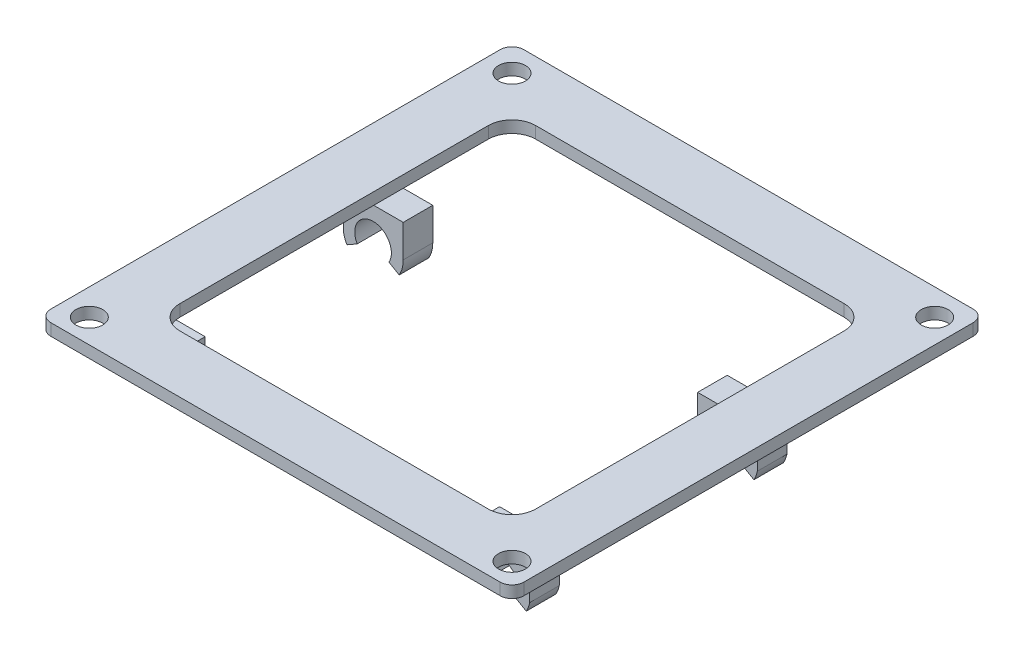
SolidWorks part; units mm, degrees
ref_plane "Front Plane" through (0, 0, 0) normal (0, 0, 1) x (1, 0, 0)
ref_plane "Top Plane" through (0, 0, 0) normal (0, 1, 0) x (1, 0, 0)
ref_plane "Right Plane" through (0, 0, 0) normal (1, 0, 0) x (0, 0, -1)
ref_plane "Plane5" through (0, 1.4, 0) normal (0, 1, 0) x (1, 0, 0)
sketch "Sketch1" plane through (0, 1.4, 0) normal (0, 1, 0) x (1, 0, 0)
  line L0 (-30, 40.97) -> (30, 40.97) construction
  line L1 (35, -16.53) -> (-35, -16.53)
  line L2 (35, -16.53) -> (35, 40.97)
  line L3 (35, 40.97) -> (-35, 40.97)
  line L4 (-35, -16.53) -> (-35, 40.97)
  line L5 (35, -16.53) -> (-35, 40.97) construction
  line L6 (35, 40.97) -> (-35, -16.53) construction
  line L8 (45.85, -16.53) -> (-45.85, -16.53) construction
  line L9 (0, 0) -> (0, 83.8599) construction
  point P0 (-14.8765, 0)
  point P13 (0, 12.22)
  dimension "D1" = 70
extrude "Boss-Extrude1" add sketch "Sketch1" along normal blind 8
sketch "Sketch3" plane through (0, 0, -36.97) normal (0, 0, -1) x (-1, 0, 0)
  line L0 (-35, 1.4) -> (-35, -5.105)
  line L1 (-24.9, -4.1) -> (-24.9, 1.4)
  line L2 (0, 0) -> (0, -23.3047) construction
  line L3 (-35, 1.4) -> (-24.9, 1.4)
  line L4 (-35, 1.4) -> (35, 1.4) construction
  line L5 (35, 1.4) -> (24.9, 1.4)
  line L6 (24.9, -4.1) -> (24.9, 1.4)
  line L7 (35, 1.4) -> (35, -5.105)
  arc A0 (-35, -5.105) -> (-24.9, -4.1) centre (-30, -4.1) ccw
  circle A2 centre (-30, -4.1) radius 3.1
  circle A4 centre (30, -4.1) radius 3.1
  arc A6 (35, -5.105) -> (24.9, -4.1) centre (30, -4.1) cw
  dimension "D1" = 2
  dimension "D2" = 6.2
extrude "Boss-Extrude2" add sketch "Sketch3" against normal blind 5 from offset 2 contours A0 L0 L3 L1 A2 | L7 A6 L6 L5 A4 region at (29.95, 1.2536, -36.97) region at (-34.8536, -1.8525, -36.97) offset against normal yes
ref_plane "Plane1" through (0, 0, -13.22) normal (0, 0, 1) x (1, 0, 0)
mirror "Mirror1" about plane through (0, 0, -13.22) normal (0, 0, 1) of "Boss-Extrude2"
sketch "Sketch4" plane through (0, 0, -29.97) normal (0, 0, -1) x (-1, 0, 0)
  line L0 (-30, -4.1) -> (-20, -9.8735)
  line L1 (-20, -9.8735) -> (-40, -9.8735)
  line L2 (-40, -9.8735) -> (-30, -4.1)
  line L3 (0, 0) -> (0, -31.947) construction
  line L4 (20, -9.8735) -> (40, -9.8735)
  line L5 (30, -4.1) -> (20, -9.8735)
  line L6 (40, -9.8735) -> (30, -4.1)
  dimension "D1" = 20
  dimension "D2" = 120
extrude "Cut-Extrude1" cut sketch "Sketch4" against normal blind 63 and the other way blind 10
other "Move Face1" flip direction yes face at (0, 9.4, -12.22) offset 6 parameters "D1"=6
sketch "Sketch5" plane through (0, 3.4, 0) normal (0, 1, 0) x (1, 0, 0)
  line L0 (-40, -16.53) -> (-35, -16.53) construction
  line L1 (40, 63.47) -> (-40, 63.47)
  line L2 (40, 63.47) -> (40, -16.53)
  line L3 (40, -16.53) -> (-40, -16.53)
  line L4 (-40, 63.47) -> (-40, -16.53)
  line L5 (40, 63.47) -> (-40, -16.53) construction
  line L6 (40, -16.53) -> (-40, 63.47) construction
  line L7 (-35, 40.97) -> (-35, -16.53) construction
  line L8 (35, -16.53) -> (40, -16.53) construction
  line L9 (35, -16.53) -> (35, 40.97) construction
  line L10 (-35, -16.53) -> (35, -16.53) construction
  point P0 (0, 23.47)
  dimension "D1" = 80
  dimension "D2" = 80
extrude "Boss-Extrude3" add sketch "Sketch5" against normal blind 2
fillet "Fillet1" radius 2 4 edges at (-40, 2.4, -63.47) (-40, 2.4, 16.53) (40, 2.4, 16.53) (40, 2.4, -63.47)
sketch "Sketch6" plane through (0, 3.4, 0) normal (0, 1, 0) x (1, 0, 0)
  line L0 (35.9551, 59.0149) -> (39.4142, 62.8842) construction
  line L1 (35.9551, 59.0149) -> (-35.5449, 59.0149) construction
  line L2 (35.9551, 59.0149) -> (35.9551, -12.4851) construction
  line L3 (35.9551, -12.4851) -> (-35.5449, -12.4851) construction
  line L4 (-35.5449, 59.0149) -> (-35.5449, -12.4851) construction
  line L5 (-35.5449, -12.4851) -> (-39.4142, -15.9442) construction
  circle A0 centre (35.9551, 59.0149) radius 2.275
  circle A1 centre (35.9551, -12.4851) radius 2.275
  circle A2 centre (-35.5449, 59.0149) radius 2.275
  circle A3 centre (-35.5449, -12.4851) radius 2.275
  arc A4 (40, 61.47) -> (38, 63.47) centre (38, 61.47) ccw construction
  arc A5 (-40, -14.53) -> (-38, -16.53) centre (-38, -14.53) ccw construction
  dimension "D2" = 4.55
  dimension "D1" = 71.5
extrude "Cut-Extrude2" cut sketch "Sketch6" against normal blind 2
sketch "Sketch7" plane through (0, 3.4, 0) normal (0, 1, 0) x (1, 0, 0)
  line L0 (35.9551, 59.0149) -> (-35.5449, -12.4851) construction
  line L2 (-29.8881, -6.8282) -> (30.2982, -6.8282)
  line L3 (-29.8881, -6.8282) -> (-29.8881, 53.3581)
  line L4 (-29.8881, 53.3581) -> (30.2982, 53.3581)
  line L5 (30.2982, -6.8282) -> (30.2982, 53.3581)
  line L6 (-29.8881, -6.8282) -> (30.2982, 53.3581) construction
  line L7 (-29.8881, 53.3581) -> (30.2982, -6.8282) construction
  point P4 (0.2051, 23.2649)
  dimension "D1" = 8
extrude "Cut-Extrude3" cut sketch "Sketch7" against normal blind 2
fillet "Fillet2" radius 4 4 edges at (30.2982, 2.4, -53.3581) (30.2982, 2.4, 6.8282) (-29.8881, 2.4, 6.8282) (-29.8881, 2.4, -53.3581)
